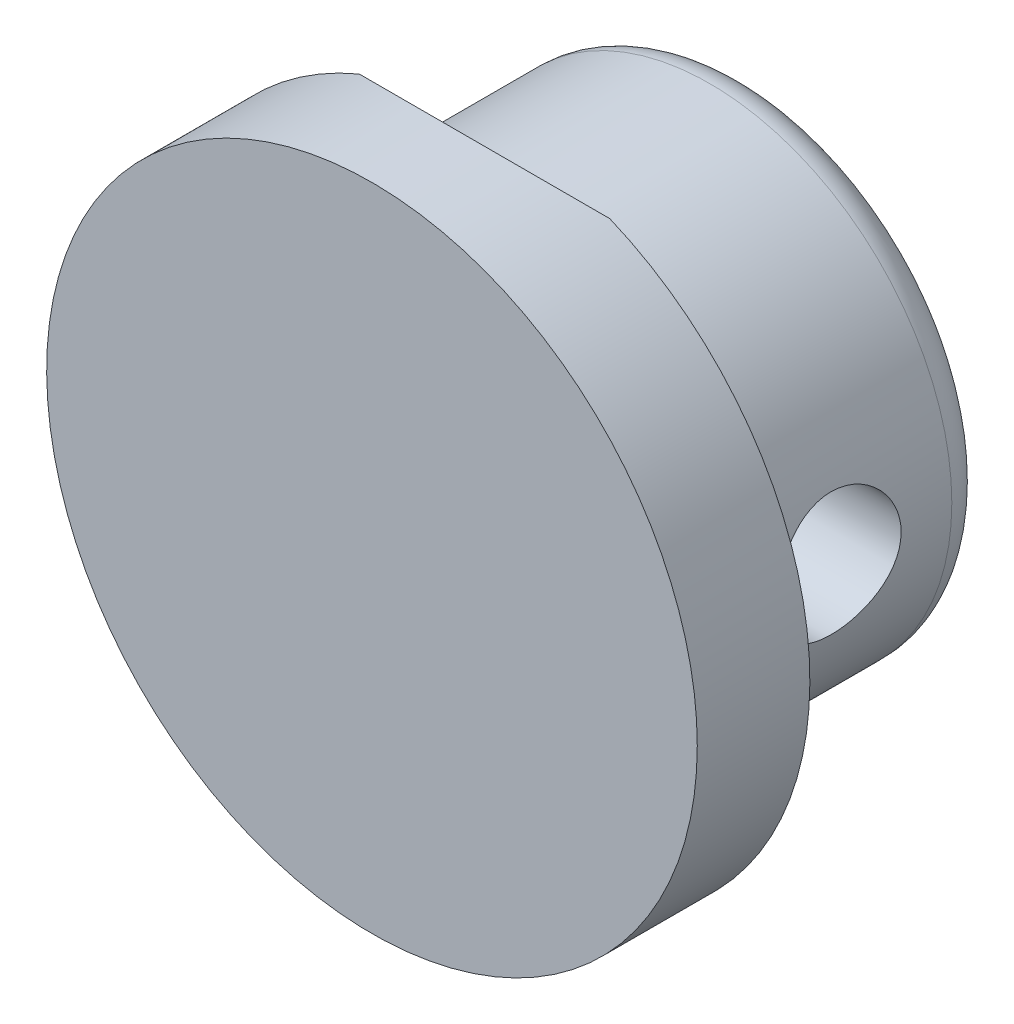
SolidWorks part; units mm, degrees
ref_plane "正面(Front)" through (0, 0, 0) normal (0, 0, 1) x (1, 0, 0)
ref_plane "平面(Top)" through (0, 0, 0) normal (0, 1, 0) x (1, 0, 0)
ref_plane "右側面(Right)" through (0, 0, 0) normal (1, 0, 0) x (0, 0, -1)
sketch "ｽｹｯﾁ1" plane through (0, 0, 0) normal (0, 0, 1) x (1, 0, 0)
  circle A0 centre (0, 0) radius 6.45
  dimension "D1" = 12.9
extrude "ﾎﾞｽ - 押し出し1" add sketch "ｽｹｯﾁ1" along normal blind 7
sketch "ｽｹｯﾁ2" plane through (0, 0, 7) normal (0, 0, 1) x (1, 0, 0)
  line L1 (-14.75, 9) -> (14.75, 9)
  line L2 (-14.75, 9) -> (-14.75, -9)
  line L3 (-14.75, -9) -> (14.75, -9)
  line L4 (14.75, 9) -> (14.75, -9)
  line L5 (-14.75, 9) -> (14.75, -9) construction
  line L6 (-14.75, -9) -> (14.75, 9) construction
  point P0 (0, 0)
  dimension "D1" = 18
  dimension "D2" = 29.5
extrude "ﾎﾞｽ - 押し出し2" add sketch "ｽｹｯﾁ2" along normal blind 3
sketch "ｽｹｯﾁ3" plane through (0, 0, 0) normal (1, 0, 0) x (0, 0, -1)
  line L0 (-10, 9) -> (-23.3333, 13.714)
  line L1 (-28.0696, 5.0531) -> (-10, -9)
  line L2 (-10, 9) -> (-42.4502, 9) construction
  line L4 (-10, 9) -> (-10, -9)
  arc A0 (-23.3333, 13.714) -> (-28.0696, 5.0531) centre (-25, 9) ccw
  circle A1 centre (-25, 9) radius 1.65
  dimension "D2" = 5
  dimension "D3" = 3.3
  dimension "D1" = 15
extrude "ﾎﾞｽ - 押し出し3" add sketch "ｽｹｯﾁ3" against normal blind 5 from surface starting at face at (14.75, 0, 8.5)
extrude "ﾎﾞｽ - 押し出し4" add sketch "ｽｹｯﾁ3<2>" along normal blind 5 from surface starting at face at (-14.75, 0, 8.5)
sketch "ｽｹｯﾁ3<2>" plane through (0, 0, 0) normal (1, 0, 0) x (0, 0, -1) same geometry as "ｽｹｯﾁ3"
sketch "ｽｹｯﾁ4" plane through (0, -9, 0) normal (0, -1, 0) x (1, 0, 0)
  line L6 (-14.75, 7) -> (14.75, 7)
  line L7 (14.75, 7) -> (14.75, 10)
  line L8 (14.75, 10) -> (9.75, 10)
  line L9 (9.75, 10) -> (-9.75, 10)
  line L10 (-9.75, 10) -> (-14.75, 10)
  line L11 (-14.75, 10) -> (-14.75, 7)
  line L12 (-14.75, 7) -> (14.75, 7)
  line L13 (14.75, 7) -> (14.75, 10)
  line L14 (14.75, 10) -> (9.75, 10)
  line L15 (9.75, 10) -> (-9.75, 10)
  line L16 (-9.75, 10) -> (-14.75, 10)
  line L17 (-14.75, 10) -> (-14.75, 7)
  dimension "D1" = 0
extrude "ﾎﾞｽ - 押し出し5" add sketch "ｽｹｯﾁ4" along normal blind 10
fillet "ﾌｨﾚｯﾄ1" radius 5 2 edges at (-14.75, -19, 8.5) (14.75, -19, 8.5)
sketch "ｽｹｯﾁ5" plane through (0, 0, 10) normal (0, 0, 1) x (1, 0, 0)
  line L0 (0, 0) -> (0, -31.2468) construction
  line L1 (9.75, -9) -> (14.75, -9) construction
  line L2 (-9.75, 5.0531) -> (-9.75, -9) construction
  circle A0 centre (0, -14) radius 2.5
  circle A1 centre (-9.75, -14) radius 2.5
  circle A2 centre (9.75, -14) radius 2.5
  dimension "D1" = 5
  dimension "D2" = 5
  dimension "D3" = 5
extrude "ｶｯﾄ - 押し出し1" cut sketch "ｽｹｯﾁ5" against normal through all
chamfer "面取り1" distance 1 angle 45 6 edges at (12.25, -14, 7) (2.5, -14, 7) (-7.25, -14, 7) (-7.25, -14, 10) (2.5, -14, 10) (7.25, -14, 10)
chamfer "面取り2" distance 1 angle 45 9 edges at (-14.75, 9, 8.5) (0, 9, 7) (14.75, 9, 8.5) (-14.75, 11.357, 16.6667) (-14.75, 11.399, 29.3869) (-14.75, -1.9734, 19.0348) (14.75, 11.357, 16.6667) (14.75, 11.399, 29.3869) (14.75, -1.9734, 19.0348)
sketch "ｽｹｯﾁ6" plane through (0, 0, 0) normal (1, 0, 0) x (0, 0, -1)
  line L0 (0, 0) -> (-31.3812, 0) construction
  line L1 (0, -6.45) -> (0, 6.45) construction
  line L2 (-5.4289, -0.825) -> (-5.9053, 0)
  line L3 (-5.9053, 0) -> (-5.4289, 0.825)
  arc A0 (-5.4289, -0.825) -> (-5.4289, 0.825) centre (-4, 0) ccw
  dimension "D1" = 3.3
  dimension "D2" = 4
  dimension "D3" = 60
extrude "ｶｯﾄ - 押し出し2" cut sketch "ｽｹｯﾁ6" against normal through all both and the other way through all
fillet "ﾌｨﾚｯﾄ2" radius 1 1 edges at (6.45, 0, 0)
sketch "ｽｹｯﾁ7" plane through (0, 0, 0) normal (0, 0, -1) x (-1, 0, 0)
  circle A0 centre (0, 0) radius 8.6678
extrude "ｶｯﾄ - 押し出し3" cut sketch "ｽｹｯﾁ7" against normal through all both and the other way through all flip side to cut
